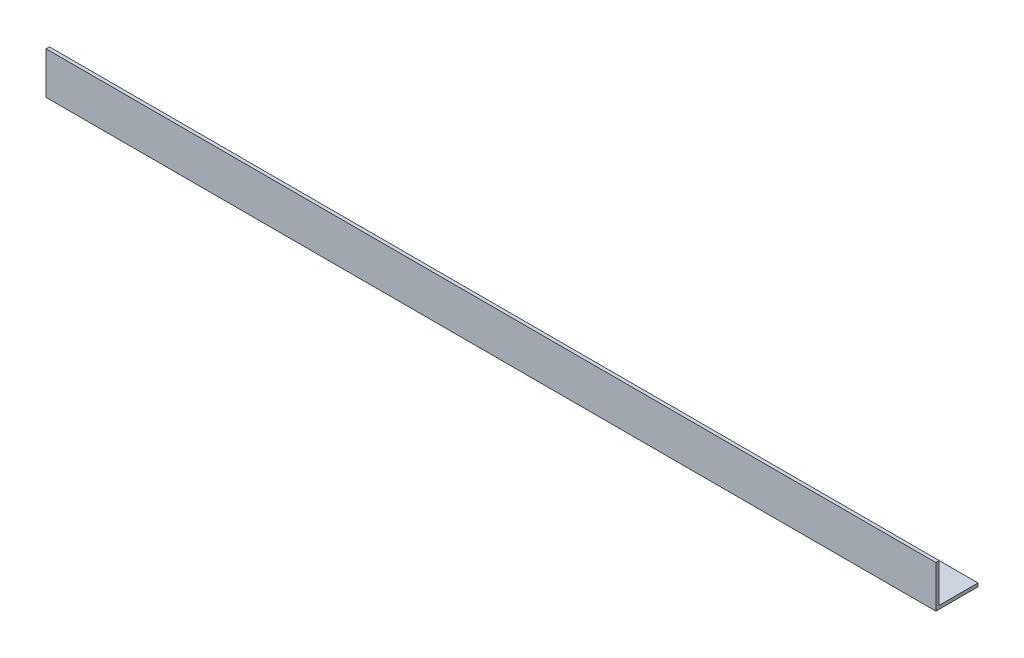
SolidWorks part; units mm, degrees
ref_plane "Спереди" through (0, 0, 0) normal (0, 0, 1) x (1, 0, 0)
ref_plane "Сверху" through (0, 0, 0) normal (0, 1, 0) x (1, 0, 0)
ref_plane "Справа" through (0, 0, 0) normal (1, 0, 0) x (0, 0, -1)
sketch "Эскиз1" plane through (0, 0, 0) normal (1, 0, 0) x (0, 0, -1)
  line L0 (0, 25) -> (0, 0)
  line L1 (0, 0) -> (25, 0)
extrude "Вытянуть-Тонкостенный1" add sketch "Эскиз1" along normal blind 528 thin thin type one direction reverse wall 2
